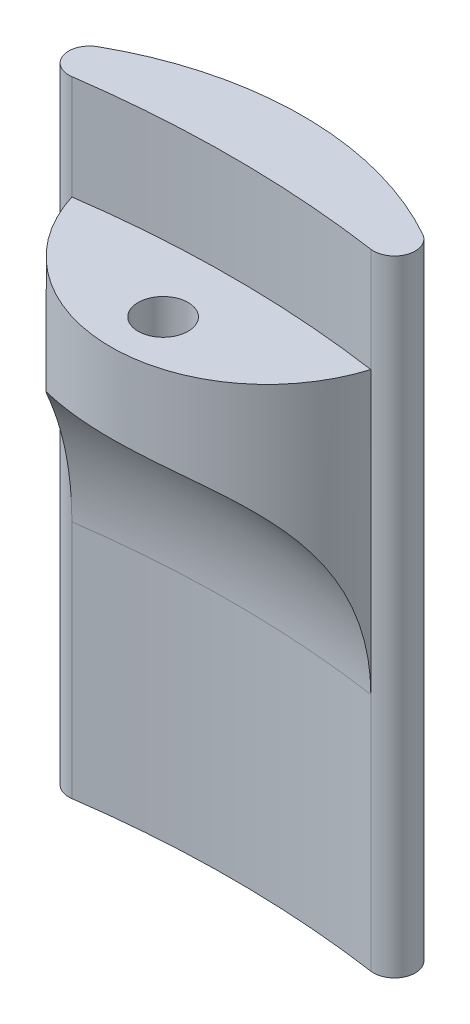
SolidWorks part; units mm, degrees
ref_plane "Front Plane" through (0, 0, 0) normal (0, 0, 1) x (1, 0, 0)
ref_plane "Top Plane" through (0, 0, 0) normal (0, 1, 0) x (1, 0, 0)
ref_plane "Right Plane" through (0, 0, 0) normal (1, 0, 0) x (0, 0, -1)
sketch "Sketch1" plane through (0, 0, 0) normal (0, 1, 0) x (1, 0, 0)
  circle A0 centre (0, 0) radius 101.0285
  circle A1 centre (0, 0) radius 94.415
  circle A2 centre (0, 94.415) radius 2.4
  point P6 (0, 94.415)
  dimension "D1" = 202.057
  dimension "D2" = 188.83
  dimension "D3" = 4.8
sketch "Sketch2" plane through (0, 0, 0) normal (0, 1, 0) x (1, 0, 0)
  line L0 (0, 0) -> (0, 101.0285) construction
  arc A0 (-22.5, 98.4912) -> (22.5, 98.4912) centre (0, 0) cw
  circle A1 centre (0, 0) radius 101.0285 construction
  arc A2 (-22.5, 98.4912) -> (22.5, 98.4912) centre (0, 76.0285) cw
  point P8 (29.3625, 96.6675)
  dimension "D1" = 25
  dimension "D2" = 45
extrude "Boss-Extrude1" add sketch "Sketch2" along normal blind 10 and the other way blind 50
fillet "Fillet1" radius 2 2 edges at (-22.5, -20, -98.4912) (22.5, -20, -98.4912)
sketch "Sketch3" plane through (0, 0, 0) normal (0, 1, 0) x (1, 0, 0)
  circle A0 centre (0, 94.415) radius 2.4 construction
  circle A1 centre (0, 94.415) radius 2.4
  arc A2 (14.3414, 100.0054) -> (-14.3414, 100.0054) centre (0, 0) ccw construction
  arc A3 (14.3414, 100.0054) -> (-14.3414, 100.0054) centre (0, 0) ccw
  arc A4 (-14.3414, 100.0054) -> (14.3414, 100.0054) centre (0, 104.4014) ccw
  dimension "D1" = 15
extrude "Boss-Extrude2" add sketch "Sketch3" against normal blind 5
fillet "Fillet2" radius 22 1 edges at (0, -5, -101.0285)
